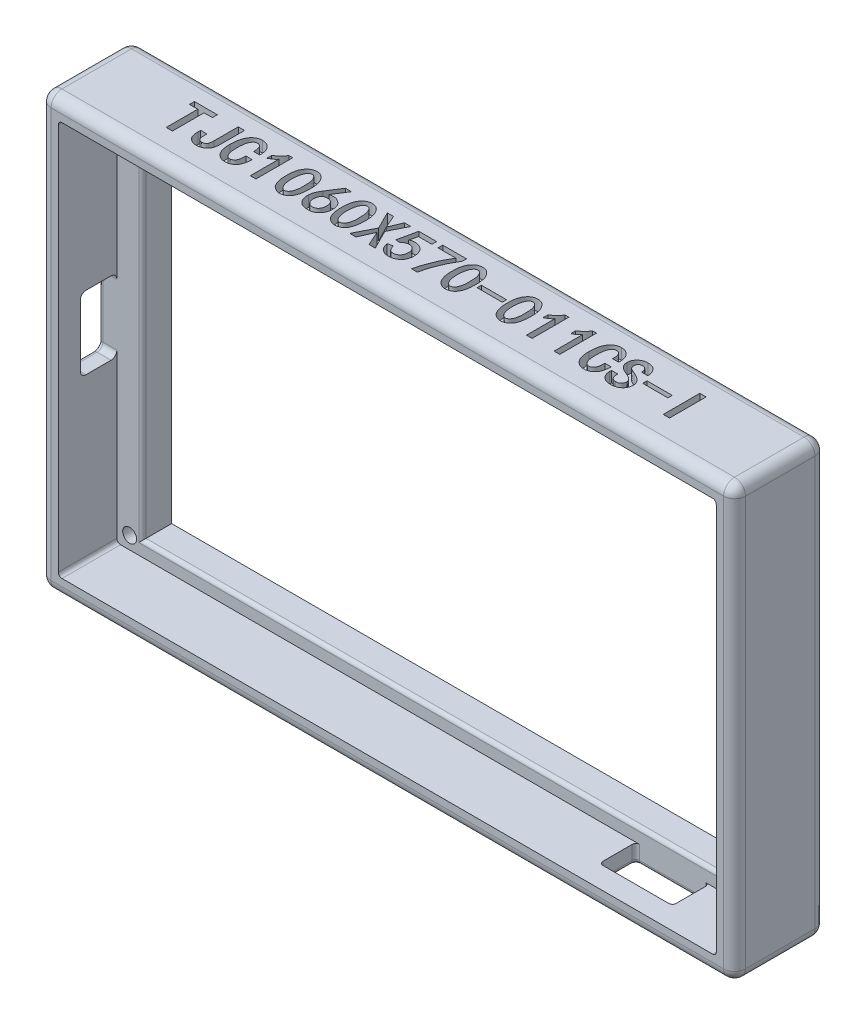
SolidWorks part; units mm, degrees
material "PBT 一般用途"
ref_plane "前视基准面" through (0, 0, 0) normal (0, 0, 1) x (1, 0, 0)
ref_plane "上视基准面" through (0, 0, 0) normal (0, 1, 0) x (1, 0, 0)
ref_plane "右视基准面" through (0, 0, 0) normal (1, 0, 0) x (0, 0, -1)
sketch "草图1" plane through (0, 0, 0) normal (0, 0, 1) x (1, 0, 0)
  line L0 (-79.4262, 67.4676) -> (110.5738, 67.4676)
  line L1 (110.5738, 67.4676) -> (110.5738, -50.5324)
  line L2 (110.5738, -50.5324) -> (-79.4262, -50.5324)
  line L3 (-79.4262, -50.5324) -> (-79.4262, 67.4676)
  dimension "D1" = 190
  dimension "D2" = 118
extrude "凸台-拉伸1" add sketch "草图1" along normal blind 9
sketch "草图2" plane through (0, 0, 0) normal (0, 0, -1) x (-1, 0, 0)
  line L0 (-98.5738, 59.4676) -> (67.4262, 59.4676)
  line L1 (67.4262, 59.4676) -> (67.4262, -41.5324)
  line L2 (67.4262, -41.5324) -> (-98.5738, -41.5324)
  line L3 (-98.5738, -41.5324) -> (-98.5738, 59.4676)
  line L4 (79.4262, 67.4676) -> (79.4262, -50.5324) construction
  line L5 (-110.5738, 67.4676) -> (79.4262, 67.4676) construction
  point P2 (-128.9101, 99.93)
  dimension "D1" = 166
  dimension "D2" = 101
  dimension "D3" = 12
  dimension "D4" = 8
extrude "切除-拉伸1" cut sketch "草图2" along direction (0, 0, -1) on the side against the normal up to next (9 mm away)
chamfer "倒角1" distance 1 angle 45 4 edges at (-67.4262, 8.9676, 0) (15.5738, -41.5324, 0) (98.5738, 8.9676, 0) (15.5738, 59.4676, 0)
sketch "草图3" plane through (0, 0, 9) normal (0, 0, 1) x (1, 0, 0)
  line L0 (-67.4262, -41.5324) -> (-59.4262, -41.5324)
  line L1 (-67.4262, -41.5324) -> (98.5738, -41.5324) construction
  line L2 (-59.4262, -41.5324) -> (-34.4262, -41.5324)
  line L3 (-34.4262, -41.5324) -> (-34.4262, -45.5324)
  line L4 (-34.4262, -45.5324) -> (-59.4262, -45.5324)
  line L5 (-59.4262, -45.5324) -> (-59.4262, -41.5324)
  line L6 (-74.4262, 62.4676) -> (105.5738, 62.4676) construction
  line L7 (105.5738, 62.4676) -> (105.5738, -45.5324) construction
  line L8 (105.5738, -45.5324) -> (-74.4262, -45.5324) construction
  line L9 (-74.4262, -45.5324) -> (-74.4262, 62.4676) construction
  line L10 (110.5738, -50.5324) -> (110.5738, 67.4676) construction
  line L11 (-79.4262, -50.5324) -> (110.5738, -50.5324) construction
  line L18 (-79.4262, 67.4676) -> (-79.4262, -50.5324)
  line L19 (110.5738, 67.4676) -> (-79.4262, 67.4676)
  line L20 (110.5738, -50.5324) -> (110.5738, 67.4676)
  line L21 (-79.4262, -50.5324) -> (110.5738, -50.5324)
  line L22 (-79.4262, 67.4676) -> (-79.4262, -50.5324)
  line L23 (110.5738, 67.4676) -> (-79.4262, 67.4676)
  line L24 (110.5738, -50.5324) -> (110.5738, 67.4676)
  line L25 (-79.4262, -50.5324) -> (110.5738, -50.5324)
  circle A0 centre (102.0738, 58.9676) radius 1.9
  circle A1 centre (102.0738, -42.0324) radius 1.9
  circle A2 centre (-70.9262, -42.0324) radius 1.9
  circle A3 centre (-70.9262, 58.9676) radius 1.9
  point P28 (0, 0)
  point P30 (101.2738, -45.5324)
  point P31 (147.253, -48.0654)
  point P32 (-72.2617, -44.2559)
  dimension "D8" = 3.5
  dimension "D10" = 3.8
  dimension "D13" = 3.8
  dimension "D17" = 3.8
  dimension "D20" = 3.8
  dimension "D1" = 8
  dimension "D2" = 25
  dimension "D3" = 4
  dimension "D4" = 180
  dimension "D5" = 108
  dimension "D6" = 5
  dimension "D7" = 5
  dimension "D9" = 3.5
  dimension "D11" = 0
  dimension "D12" = 3.5
  dimension "D14" = 3.5
  dimension "D15" = 3.5
  dimension "D16" = 3.5
  dimension "D18" = 3.5
  dimension "D19" = 3.5
extrude "切除-拉伸5" cut sketch "草图3" against normal blind 6 contours A0 | A3
sketch "草图4" plane through (0, 0, 9) normal (0, 0, 1) x (1, 0, 0)
  line L0 (-74.4262, 62.4676) -> (105.5738, 62.4676)
  line L1 (105.5738, 62.4676) -> (105.5738, -45.5324)
  line L2 (105.5738, -45.5324) -> (-74.4262, -45.5324)
  line L3 (-74.4262, -45.5324) -> (-74.4262, 62.4676)
  line L4 (110.5738, 67.4676) -> (-79.4262, 67.4676) construction
  line L5 (110.5738, -50.5324) -> (110.5738, 67.4676) construction
  circle A0 centre (102.0738, -42.0324) radius 1.9
  circle A1 centre (-70.9262, -42.0324) radius 1.9
  dimension "D7" = 3.8
  dimension "D10" = 3.8
  dimension "D1" = 180
  dimension "D2" = 108
  dimension "D3" = 5
  dimension "D4" = 5
  dimension "D5" = 3.5
  dimension "D6" = 3.5
  dimension "D8" = 3.5
  dimension "D9" = 3.5
extrude "切除-拉伸7" cut sketch "草图4" against normal blind 6 contours A0
sketch "草图5" plane through (0, 0, 9) normal (0, 0, 1) x (1, 0, 0)
  line L0 (-74.4262, 62.4676) -> (105.5738, 62.4676)
  line L1 (105.5738, 62.4676) -> (105.5738, -45.5324)
  line L2 (105.5738, -45.5324) -> (-74.4262, -45.5324)
  line L3 (-74.4262, -45.5324) -> (-74.4262, 62.4676)
  line L4 (110.5738, 67.4676) -> (-79.4262, 67.4676) construction
  line L5 (110.5738, -50.5324) -> (110.5738, 67.4676) construction
  circle A0 centre (-70.9262, -42.0324) radius 1.9
  dimension "D7" = 3.8
  dimension "D1" = 180
  dimension "D2" = 108
  dimension "D3" = 5
  dimension "D4" = 5
  dimension "D5" = 3.5
  dimension "D6" = 3.5
extrude "切除-拉伸8" cut sketch "草图5" against normal blind 6 contours A0
sketch "草图6" plane through (0, 0, 9) normal (0, 0, 1) x (1, 0, 0)
  line L0 (-74.4262, 62.4676) -> (105.5738, 62.4676)
  line L1 (105.5738, 62.4676) -> (105.5738, -45.5324)
  line L2 (105.5738, -45.5324) -> (-74.4262, -45.5324)
  line L3 (-74.4262, -45.5324) -> (-74.4262, 62.4676)
  line L4 (110.5738, 67.4676) -> (-79.4262, 67.4676) construction
  line L5 (110.5738, -50.5324) -> (110.5738, 67.4676) construction
  line L6 (-79.4262, 67.4676) -> (110.5738, 67.4676)
  line L7 (110.5738, 67.4676) -> (110.5738, -50.5324)
  line L8 (110.5738, -50.5324) -> (-79.4262, -50.5324)
  line L9 (-79.4262, -50.5324) -> (-79.4262, 67.4676)
  dimension "D1" = 180
  dimension "D2" = 108
  dimension "D3" = 5
  dimension "D4" = 5
extrude "凸台-拉伸4" add sketch "草图6" along normal blind 16 contours L9 L6 L7 L8
sketch "草图7" plane through (0, 0, 25) normal (0, 0, 1) x (1, 0, 0)
  line L0 (-74.4262, 62.4676) -> (105.5738, 62.4676)
  line L1 (105.5738, 62.4676) -> (105.5738, -45.5324)
  line L2 (105.5738, -45.5324) -> (-74.4262, -45.5324)
  line L3 (-74.4262, -45.5324) -> (-74.4262, 62.4676)
  line L4 (-79.4262, -50.5324) -> (-79.4262, 67.4676) construction
  line L5 (-79.4262, 67.4676) -> (110.5738, 67.4676) construction
  dimension "D1" = 180
  dimension "D2" = 108
  dimension "D3" = 5
  dimension "D4" = 5
extrude "切除-拉伸9" cut sketch "草图7" against normal blind 16
sketch "草图9" plane through (0, 67.4676, 0) normal (0, 1, 0) x (1, 0, 0)
  text T0 "TJC1060X570-011CS-I" font "楷体" height 10
extrude "切除-拉伸10" cut sketch "草图9" against normal blind 3
fillet "圆角1" radius 3 4 edges at (15.5738, -50.5324, 0) (110.5738, 8.4676, 0) (15.5738, 67.4676, 0) (-79.4262, 8.4676, 0)
fillet "圆角2" radius 3 8 edges at (-78.5475, 66.5889, 0.8787) (-78.5475, -49.6538, 0.8787) (109.6951, -49.6538, 0.8787) (109.6951, 66.5889, 0.8787) (-79.4262, 67.4676, 14) (-79.4262, -50.5324, 14) (110.5738, -50.5324, 14) (110.5738, 67.4676, 14)
fillet "圆角3" radius 1 1 edges at (105.5738, -45.5324, 17)
fillet "圆角4" radius 1 3 edges at (105.5738, 62.4676, 17) (-74.4262, 62.4676, 17) (-74.4262, -45.5324, 17)
fillet "圆角5" radius 1 4 edges at (98.5738, 8.9676, 9) (15.5738, -41.5324, 9) (-67.4262, 8.9676, 9) (15.5738, 59.4676, 9)
sketch "草图11" plane through (0, 0, 9) normal (0, 0, 1) x (1, 0, 0)
  line L0 (-66.4262, 62.4676) -> (-66.4262, 59.9676)
  line L1 (104.5738, 62.4676) -> (-73.4262, 62.4676) construction
  line L2 (-66.4262, 59.9676) -> (-74.4262, 59.9676)
  line L3 (-74.4262, 61.4676) -> (-74.4262, -44.5324) construction
  line L4 (-66.4262, 59.9676) -> (-40.4262, 59.9676)
  line L5 (-40.4262, 59.9676) -> (-40.4262, 62.4676)
  line L6 (-40.4262, 62.4676) -> (-66.4262, 62.4676)
  line L7 (-66.4262, 62.4676) -> (-66.4262, 63.4676)
  line L8 (-66.4262, 63.4676) -> (-40.4262, 63.4676)
  line L9 (-40.4262, 63.4676) -> (-40.4262, 62.4676)
  line M7 (-68.4262, 60.4676) -> (99.5738, 60.4676)
  line M15 (104.5738, 62.4676) -> (-73.4262, 62.4676)
  dimension "D1" = 8
  dimension "D2" = 2.5
  dimension "D3" = 26
  dimension "D4" = 1
extrude "切除-拉伸14" cut sketch "草图11" along normal blind 16 contours L9 L8 L7 M15 | L5 L0 M7 M15
fillet "圆角6" radius 0.5 4 edges at (-66.4262, 63.4676, 17) (-40.4262, 63.4676, 17) (-40.4262, 62.4676, 17) (-66.4262, 62.4676, 17)
sketch "草图12" plane through (0, 0, 9) normal (0, 0, 1) x (1, 0, 0)
  line L0 (-40.9262, 63.4676) -> (97.5738, 63.4676)
  line L1 (97.5738, 63.4676) -> (97.5738, 61.9676)
  line L2 (97.5738, 61.9676) -> (105.5738, 61.9676)
  line L3 (105.5738, -44.5324) -> (105.5738, 61.4676) construction
  line L4 (97.5738, 61.9676) -> (-40.9262, 61.9676)
  line L5 (-40.9262, 61.9676) -> (-40.9262, 63.4676)
  dimension "D1" = 8
  dimension "D2" = 1.5
extrude "切除-拉伸15" cut sketch "草图12" along normal blind 16 contours L4 L5 L0 L1
fillet "圆角7" radius 0.5 2 edges at (97.5738, 63.4676, 17) (97.5738, 62.4676, 17)
sketch "草图13" plane through (0, 0, 9) normal (0, 0, 1) x (1, 0, 0)
  line L0 (105.5738, -43.5324) -> (67.5738, -43.5324)
  line L1 (105.5738, -44.5324) -> (105.5738, 61.4676) construction
  line L2 (67.5738, -43.5324) -> (67.5738, -45.5324)
  line L3 (-73.4262, -45.5324) -> (104.5738, -45.5324) construction
  line L4 (67.5738, -45.5324) -> (87.5738, -45.5324)
  line L5 (87.5738, -45.5324) -> (87.5738, -43.5324)
  line L6 (87.5738, -43.5324) -> (87.5738, -50.5324)
  line L7 (107.5738, -50.5324) -> (-76.4262, -50.5324) construction
  line L8 (87.5738, -50.5324) -> (67.5738, -50.5324)
  line L9 (67.5738, -50.5324) -> (67.5738, -43.5324)
  line M13 (-73.4262, -45.5324) -> (104.5738, -45.5324)
  dimension "D1" = 18
  dimension "D2" = 20
  dimension "D3" = 7
extrude "切除-拉伸17" cut sketch "草图13" along normal blind 10 contours L5 L0 L2 M13 | L9 L8 L6 M13
fillet "圆角8" radius 1 2 edges at (67.5738, -48.0324, 19) (87.5738, -48.0324, 19)
fillet "圆角9" radius 1 2 edges at (67.5738, -48.0324, 9) (87.5738, -48.0324, 9)
sketch "草图15" plane through (0, 0, 9) normal (0, 0, 1) x (1, 0, 0)
  line L0 (-72.7361, 62.4676) -> (-72.7361, 18.4676)
  line L1 (-66.9262, 62.4676) -> (-73.4262, 62.4676) construction
  line L2 (-72.7361, 18.4676) -> (-80.7361, 18.4676)
  line L3 (-80.7361, 18.4676) -> (-80.7361, -1.5324)
  line L4 (-80.7361, -1.5324) -> (-72.7361, -1.5324)
  line L5 (-72.7361, -1.5324) -> (-72.7361, 18.4676)
  line M22 (-74.4262, 61.4676) -> (-74.4262, -44.5324)
  dimension "D1" = 44
  dimension "D2" = 8
  dimension "D3" = 20
extrude "切除-拉伸19" cut sketch "草图15" along normal blind 10 contours L3 L4 L2 M22 | L4 L5 L2 M22
fillet "圆角11" radius 1.6 4 edges at (-76.9262, 18.4676, 9) (-76.9262, 18.4676, 19) (-76.9262, -1.5324, 19) (-76.9262, -1.5324, 9)
fillet "圆角12" radius 3 8 edges at (-79.4262, 8.4676, 25) (15.5738, 67.4676, 25) (15.5738, -50.5324, 25) (110.5738, 8.4676, 25) (109.6951, 66.5889, 25) (109.6951, -49.6538, 25) (-78.5475, -49.6538, 25) (-78.5475, 66.5889, 25)
fillet "圆角13" radius 1.2 8 edges at (-79.4262, 17.9989, 9.4686) (-79.4262, 18.4676, 14) (-79.4262, 17.9989, 18.5314) (-79.4262, 8.4676, 19) (-79.4262, -1.0638, 18.5314) (-79.4262, -1.5324, 14) (-79.4262, -1.0638, 9.4686) (-79.4262, 8.4676, 9)
fillet "圆角14" radius 1.2 8 edges at (87.2809, -50.5324, 9.2929) (87.5738, -50.5324, 14) (87.2809, -50.5324, 18.7071) (77.5738, -50.5324, 19) (67.8667, -50.5324, 18.7071) (67.5738, -50.5324, 14) (67.8667, -50.5324, 9.2929) (77.5738, -50.5324, 9)
sketch "草图18" plane through (0, 0, 9) normal (0, 0, 1) x (1, 0, 0)
  line L0 (-65.2495, 63.4676) -> (-65.2495, 62.4676)
  line L1 (-65.9262, 63.4676) -> (97.0738, 63.4676) construction
  line L2 (-65.2495, 62.4676) -> (-68.372, 62.4676)
  line L3 (-66.9262, 62.4676) -> (-73.4262, 62.4676) construction
  line L4 (-68.372, 62.4676) -> (-68.372, 63.4676)
  line L5 (-68.372, 63.4676) -> (-65.2495, 63.4676)
  line L6 (-65.2495, 62.4676) -> (98.6606, 62.4676)
  line L7 (104.5738, 62.4676) -> (98.0738, 62.4676) construction
  line L8 (98.6606, 62.4676) -> (98.6606, 63.4676)
  line L9 (98.6606, 63.4676) -> (-65.2495, 63.4676)
  point P4 (-65.2495, 62.9676)
  arc M13 (98.0738, 62.4676) -> (97.5738, 62.9676) centre (98.0738, 62.9676) cw
  arc M14 (97.5738, 62.9676) -> (97.0738, 63.4676) centre (97.0738, 62.9676) ccw
  line M15 (97.0738, 63.4676) -> (-65.9262, 63.4676)
  arc M16 (-65.9262, 63.4676) -> (-66.4262, 62.9676) centre (-65.9262, 62.9676) ccw
  arc M17 (-66.4262, 62.9676) -> (-66.9262, 62.4676) centre (-66.9262, 62.9676) cw
extrude "凸台-拉伸6" add sketch "草图18" along normal blind 16 contours L2 L0 M15 M16 M17 | L0 L6 M13 M14 M15
sketch "草图19" plane through (0, 0, 9) normal (0, 0, 1) x (1, 0, 0)
  line L0 (105.5738, 57.473) -> (97.5738, 57.473)
  line L1 (105.5738, -44.5324) -> (105.5738, 61.4676) construction
  line L2 (97.5738, 57.473) -> (97.5738, 62.473)
  line L3 (97.5738, 62.473) -> (-12.4262, 62.473)
  line L4 (-12.4262, 62.473) -> (-12.4262, 57.473)
  line L5 (-12.4262, 57.473) -> (97.5738, 57.473)
  dimension "D1" = 110
  dimension "D2" = 8
  dimension "D3" = 5
extrude "切除-拉伸21" cut sketch "草图19" against normal blind 5 contours L2 L3 L4 L5
sketch "草图21" plane through (0, 0, 9) normal (0, 0, 1) x (1, 0, 0)
fillet "圆角17" radius 1 7 edges at (97.5738, 59.4676, 6) (97.5738, 61.4676, 9) (-12.4262, 61.4676, 9) (-12.4262, 59.7605, 8.7071) (97.5738, 59.7605, 8.7071) (42.5738, 59.4676, 4) (-12.4262, 59.4676, 6)
